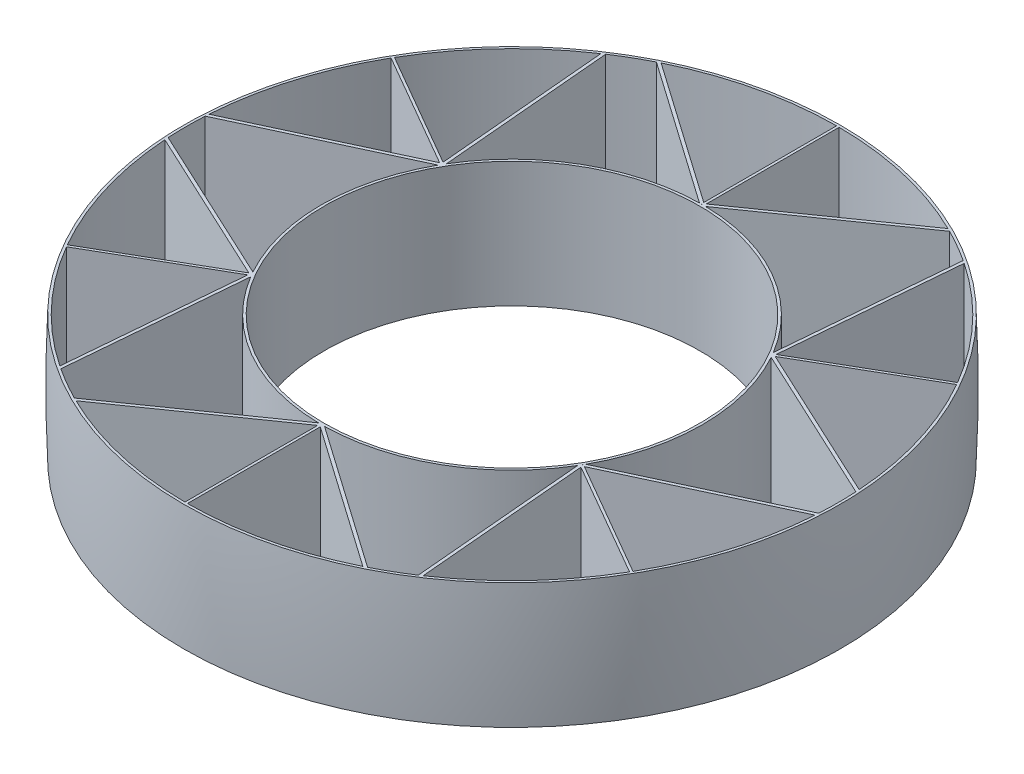
SolidWorks part; units mm, degrees
material "Бутил"
ref_plane "Спереди" through (0, 0, 0) normal (0, 0, 1) x (1, 0, 0)
ref_plane "Сверху" through (0, 0, 0) normal (0, 1, 0) x (1, 0, 0)
ref_plane "Справа" through (0, 0, 0) normal (1, 0, 0) x (0, 0, -1)
sketch "Эскиз3" plane through (0, 0, 0) normal (0, 1, 0) x (1, 0, 0)
  circle A0 centre (0, 0) radius 130
  circle A1 centre (0, 0) radius 131
  dimension "D1" = 262
  dimension "D2" = 260
sketch "Эскиз6" plane through (0, 0, 0) normal (0, 1, 0) x (1, 0, 0)
  circle A0 centre (0, 0) radius 75
  circle A1 centre (0, 0) radius 76
  dimension "D1" = 150
  dimension "D2" = 152
extrude "Бобышка-Вытянуть9" add sketch "Эскиз6" along normal blind 50 contours A1 A0 region at (-75.785, 0, 0)
extrude "Бобышка-Вытянуть10" add sketch "Эскиз3" along normal up to surface (50 mm away) up to face at (0, 50, 75)
sketch "Эскиз7" plane through (0, 0, 0) normal (0, 1, 0) x (1, 0, 0)
  line L1 (-0.5, -75.9984) -> (-0.5, -129.999)
  line L2 (0.5, -75.9984) -> (0.5, -129.999)
  line L3 (0, -130) -> (0, 0) construction
  circle A0 centre (0, 0) radius 76 construction
  arc A2 (-0.5, -75.9984) -> (0.5, -75.9984) centre (0, -48.8147) ccw
  arc A3 (-0.5, -129.999) -> (0.5, -129.999) centre (0, 0) ccw
  circle A5 centre (0, 0) radius 130 construction
  point P1 (0, -76.003)
  point P5 (0, -130)
  point P13 (0, 0)
  point P14 (0, 0)
  dimension "D4" = 27.1883
  dimension "D1" = 1
extrude "Бобышка-Вытянуть11" add sketch "Эскиз7" along normal up to surface (50 mm away) up to face at (0, 50, 75)
sketch "Эскиз4" plane through (0, 0, 0) normal (0, -1, 0) x (1, 0, 0)
  line L2 (-58.4845, 116.1015) -> (-1.2, 75.9905)
  line L4 (0.5, 129.999) -> (0.5, 75.9984) construction
  line L6 (0, 148.9306) -> (0, 117.9564) construction
  line L7 (58.4845, 116.1015) -> (1.2, 75.9905)
  line L8 (0.5, 76.9984) -> (57.2333, 116.7234)
  line L9 (0.5, 75.9984) -> (0.5, 76.9984)
  line L10 (-0.5, 76.9984) -> (-57.2333, 116.7234)
  line L11 (-0.5, 75.9984) -> (-0.5, 76.9984)
  circle A0 centre (0, 0) radius 130 construction
  arc A4 (1.2, 75.9905) -> (0.5, 75.9984) centre (0, 0) ccw
  arc A5 (57.2333, 116.7234) -> (58.4845, 116.1015) centre (0, 0) cw
  circle A6 centre (0, 0) radius 76 construction
  arc A7 (-0.5, 129.999) -> (0.5, 129.999) centre (0, 0) ccw construction
  arc A8 (-57.2333, 116.7234) -> (-58.4845, 116.1015) centre (0, 0) ccw
  arc A9 (-1.2, 75.9905) -> (-0.5, 75.9984) centre (0, 0) cw
  point P2 (0, 0)
  point P8 (3.4714, 87.6359)
  point P16 (0, 0)
  point P17 (0, 0)
  point P28 (0, 0)
  point P31 (0, 0)
  dimension "D1" = 110
  dimension "D5" = 1
  dimension "D6" = 0.7
extrude "Бобышка-Вытянуть12" add sketch "Эскиз4" against normal up to surface (50 mm away) up to face at (0, 50, 75)
sketch "Эскиз5" plane through (0, 0, 0) normal (1, 0, 0) x (0, 0, -1)
  line L0 (-131, 0) -> (-131, 50)
  line L2 (-156.6734, 25) -> (-131.9727, 25) construction
  line L4 (-131, 50) -> (-131, 0)
  line L5 (-131, 25) -> (-131, 50)
  line L7 (-131, 0) -> (-131, 50)
  line L8 (0, 0) -> (0, 64.3857) construction
  arc A3 (-131, 50) -> (-131, 0) centre (468.4789, 25) ccw
  point P2 (0, 0)
  point P3 (0, 0)
  point P4 (0, 0)
  point P5 (0, 0)
  point P6 (0, 0)
  point P8 (0, 0)
  point P9 (-134.9371, 50)
  point P13 (-138.2129, 0.7106)
  point P14 (-142.8915, 50)
  point P15 (0, 0)
  point P16 (-142.8915, 0.5598)
  point P17 (0, 0)
  point P18 (-135, 50)
  point P19 (0, 0)
  point P20 (-141.9822, 50)
  point P21 (0, 0)
  point P22 (0, 0)
  point P23 (-131.9727, 24.7882)
  point P24 (0, 0)
  point P25 (0, 0)
  point P27 (0, 0)
  dimension "D1" = 600
revolve "Повернуть2" add sketch "Эскиз5" angle 360 about L8 region at (0, 25, 131.2084)
pattern_circular "Круговой массив9" count 6 over 360 about axis through (0, 50, 0) along (0, -1, 0) of "Бобышка-Вытянуть12" reverse direction yes
pattern_circular "Круговой массив10" count 6 over 360 about axis through (0, 50, 0) along (0, -1, 0) of "Бобышка-Вытянуть11" reverse direction yes
